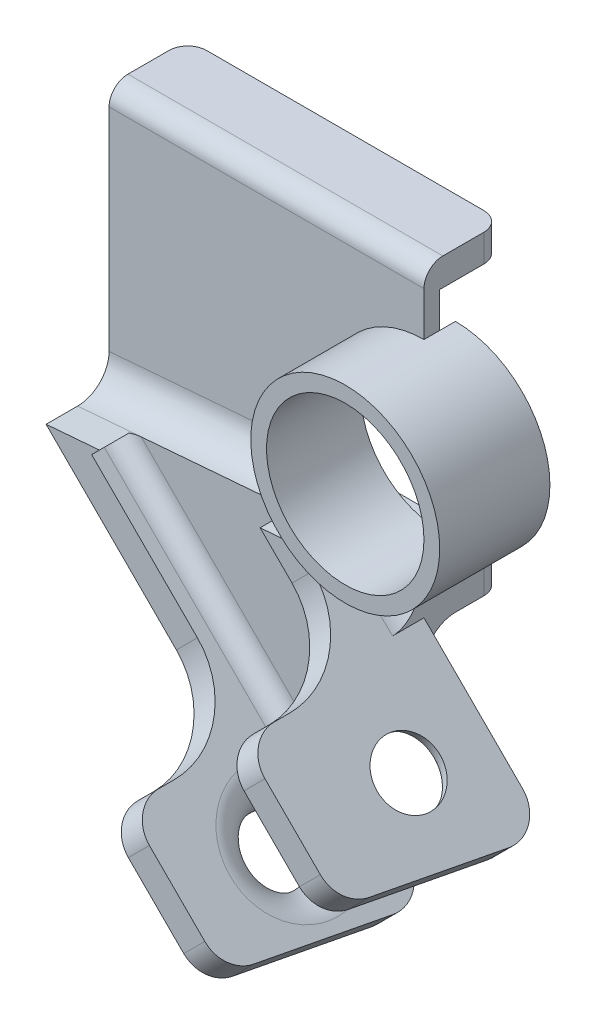
SolidWorks part; units mm, degrees
ref_plane "Alzado" through (0, 0, 0) normal (0, 0, 1) x (1, 0, 0)
ref_plane "Planta" through (0, 0, 0) normal (0, 1, 0) x (1, 0, 0)
ref_plane "Vista lateral" through (0, 0, 0) normal (1, 0, 0) x (0, 0, -1)
sketch "Croquis1" plane through (0, 0, 0) normal (0, 0, 1) x (1, 0, 0)
  circle A0 centre (0, 0) radius 6
  circle A1 centre (0, 0) radius 5
  dimension "D1" = 12
  dimension "D2" = 10
extrude "Saliente-Extruir1" add sketch "Croquis1" along normal blind 7
sketch "Croquis2" plane through (0, 0, 0) normal (0, 0, -1) x (-1, 0, 0)
  line L0 (0, -10) -> (0, -5)
  line L1 (0, -10) -> (20, -10)
  line L2 (0, 10) -> (20, 10)
  line L3 (20, -10) -> (20, 10)
  line L4 (0, 5) -> (0, 10)
  line L5 (0, 0) -> (20, 0) construction
  line L6 (0, 0) -> (0, 5.568) construction
  circle A1 centre (0, 0) radius 5 construction
  arc A2 (0, -5) -> (0, 5) centre (0, 0) ccw
  dimension "D1" = 20
  dimension "D2" = 20
  dimension "D3" = 10
extrude "Saliente-Extruir2" add sketch "Croquis2" against normal blind 2 and the other way blind 3
sketch "Croquis4" plane through (0, 0, -3) normal (0, 0, -1) x (-1, 0, 0)
  line L0 (20, -10) -> (20, 10) construction
  line L1 (20, -8.25) -> (0, -8.25)
  line L2 (20, -8.25) -> (20, 8.25)
  line L3 (20, 8.25) -> (0, 8.25)
  line L4 (0, -8.25) -> (0, 8.25)
  line L5 (0, 10) -> (0, 5) construction
  line L6 (20, 10) -> (0, 10) construction
  dimension "D1" = 16.5
  dimension "D2" = 1.75
extrude "Cortar-Extruir1" cut sketch "Croquis4" against normal blind 4
sketch "Croquis5" plane through (0, 0, 2) normal (0, 0, 1) x (1, 0, 0)
  line L0 (-3.9474, -5.3578) -> (-20, -6.6592)
  line L1 (-3.9474, -5.3578) -> (16.7598, -26.065)
  line L2 (-20, -6.6592) -> (0.7072, -27.3664)
  line L3 (16.7598, -26.065) -> (0.7072, -27.3664)
  line L4 (-20, 10) -> (0, 10) construction
  line L6 (-20, -10) -> (-20, 10) construction
  dimension "D1" = 45
extrude "Saliente-Extruir7" add sketch "Croquis5" along normal blind 4
sketch "Croquis10" plane through (0, 0, 6) normal (0, 0, 1) x (1, 0, 0)
  line L0 (-0.7652, -25.894) -> (7.9118, -17.217)
  line L1 (-20, -6.6592) -> (0.7072, -27.3664) construction
  line L2 (16.7598, -26.065) -> (-3.9474, -5.3578) construction
  line L3 (7.9118, -17.217) -> (16.7598, -26.065)
  line L4 (16.7598, -26.065) -> (0.7072, -27.3664)
  line L5 (0.7072, -27.3664) -> (-0.7652, -25.894)
extrude "Cortar-Extruir4" cut sketch "Croquis10" against normal up to surface (4 mm away) up to face at (0.1616, -16.5473, 2)
sketch "Croquis11" plane through (0, 0, 6) normal (0, 0, 1) x (1, 0, 0)
  line L0 (0.5721, -24.5568) -> (6.5825, -18.5464)
  line L1 (7.9118, -17.217) -> (-0.7652, -25.894) construction
  line L2 (6.5825, -18.5464) -> (-0.8421, -11.1217)
  line L3 (-0.8421, -11.1217) -> (-6.8526, -17.1321)
  line L4 (-6.8526, -17.1321) -> (0.5721, -24.5568)
  line L5 (7.9118, -17.217) -> (-3.9474, -5.3578) construction
  dimension "D1" = 8.5
  dimension "D2" = 10.5
  dimension "D3" = 1.88
extrude "Cortar-Extruir5" cut sketch "Croquis11" against normal blind 2.2
sketch "Croquis12" plane through (0, 0, 6) normal (0, 0, 1) x (1, 0, 0)
  line L0 (-6.8526, -17.1321) -> (-8.1898, -18.4694)
  line L1 (-20, -6.6592) -> (-0.7652, -25.894) construction
  line L2 (-8.1898, -18.4694) -> (-0.7652, -25.894)
  line L3 (-0.7652, -25.894) -> (0.5721, -24.5568)
  line L4 (0.5721, -24.5568) -> (-6.8526, -17.1321)
  line L5 (-0.8421, -11.1217) -> (0.4872, -9.7924)
  line L6 (7.9118, -17.217) -> (-3.9474, -5.3578) construction
  line L7 (0.4872, -9.7924) -> (7.9118, -17.217)
  line L8 (7.9118, -17.217) -> (6.5825, -18.5464)
  line L9 (6.5825, -18.5464) -> (-0.8421, -11.1217)
extrude "Saliente-Extruir9" add sketch "Croquis12" along normal blind 8
sketch "Croquis13" plane through (-13.3296, -13.3296, 0) normal (-0.7071, -0.7071, 0) x (0, 0, 1)
  line L0 (2, 4.7088) -> (2, -17.7688) construction
  line L1 (2, -17.7688) -> (14, -17.7688) construction
  circle A0 centre (7, -12.2688) radius 2
  dimension "D3" = 4
  dimension "D1" = 5
  dimension "D2" = 5.5
extrude "Cortar-Extruir6" cut sketch "Croquis13" against normal up to surface (12.2712 mm away) up to face at (1.2719, -10.5771, 6.5714)
fillet "Redondeo1" radius 2 2 edges at (-1.9028, -22.0819, 7) (1.2792, -13.243, 7)
sketch "Croquis14" plane through (12.5644, -12.5644, 0) normal (0.7071, -0.7071, 0) x (0, 0, -1)
  line L5 (-2, -6.5797) -> (-2, -18.8509) construction
  line L10 (-3.8, -8.4597) -> (-2, -8.4597)
  line L11 (-3.8, -8.4597) -> (-3.8, -16.9597)
  line L12 (-3.8, -16.9597) -> (-2, -16.9597)
  line L13 (-2, -8.4597) -> (-2, -16.9597)
extrude "Cortar-Extruir7" cut sketch "Croquis14" against normal blind 10.5
sketch "Croquis15" plane through (5.1398, -5.1398, 0) normal (0.7071, -0.7071, 0) x (0, 0, -1)
  line L0 (-2, -8.4597) -> (-6, -8.4597) construction
  line L1 (-6, -16.9597) -> (-4, -16.9597)
  line L2 (-6, -16.9597) -> (-6, -8.4597)
  line L3 (-6, -8.4597) -> (-4, -8.4597)
  line L4 (-4, -16.9597) -> (-4, -8.4597)
extrude "Cortar-Extruir8" cut sketch "Croquis15" against normal blind 14.5
fillet "Redondeo2" radius 2 3 edges at (-1.9737, -7.3315, 2) (-11.9737, -6.0085, 2) (-8.3296, -10, 2)
fillet "Redondeo3" radius 2 1 edges at (-18.3296, -8.3296, 2)
fillet "Redondeo4" radius 5 2 edges at (-7.5212, -17.8008, 6) (-0.1775, -10.457, 6)
sketch "Croquis16" plane through (-13.3296, -13.3296, 0) normal (-0.7071, -0.7071, 0) x (0, 0, 1)
  line L0 (2, -17.7688) -> (14, -15.9688)
  line L1 (14, -7.2688) -> (14, -17.7688) construction
  line L2 (14, -15.9688) -> (14, -17.7688)
  line L3 (14, -17.7688) -> (2, -17.7688)
  dimension "D1" = 1.8
extrude "Cortar-Extruir9" cut sketch "Croquis16" against normal up to surface (12.2712 mm away) up to face at (5.437, -14.7421, 7)
fillet "Redondeo5" radius 2 6 edges at (7.2472, -17.8817, 2) (-0.0966, -25.2254, 2) (-0.1775, -10.457, 14) (-7.5212, -17.8008, 14) (-1.3694, -23.9526, 14) (5.9744, -16.6089, 14)
fillet "Redondeo6" radius 1.2 4 edges at (-6.8526, -17.1321, 3) (-0.8421, -11.1217, 2.8984) (-11.9791, -12.0056, 4) (-3.6244, -8.3395, 4)
fillet "Redondeo7" radius 1.2 5 edges at (-10, 10, 2) (-20, 9.125, -3) (-20, -9.125, -3) (0, 9.125, -3) (0, -9.125, -3)
